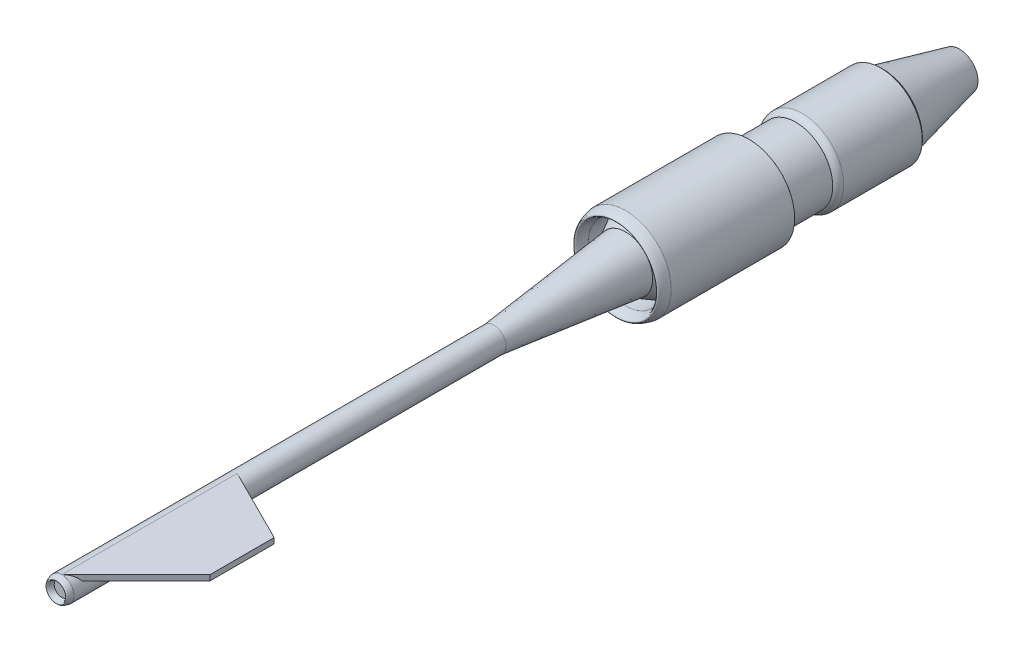
SolidWorks part; units mm, degrees
ref_plane "Front Plane" through (0, 0, 0) normal (0, 0, 1) x (1, 0, 0)
ref_plane "Top Plane" through (0, 0, 0) normal (0, 1, 0) x (1, 0, 0)
ref_plane "Right Plane" through (0, 0, 0) normal (1, 0, 0) x (0, 0, -1)
sketch "Sketch1" plane through (0, 0, 0) normal (0, 0, 1) x (1, 0, 0)
  circle A0 centre (0, 0) radius 416.25
  circle A1 centre (0, 0) radius 337.5
extrude "Boss-Extrude1" add sketch "Sketch1" against normal blind 1125
sketch "Sketch2" plane through (0, 0, 0) normal (1, 0, 0) x (0, 0, -1)
  line L0 (0, 416.25) -> (0, 337.5) construction
  line L1 (0, 337.5) -> (0, 376.875) construction
  line L2 (0, 376.875) -> (-90, 376.875) construction
  line L3 (0, 416.25) -> (0, 337.5)
  line L4 (0, 0) -> (98.8797, 0) construction
  spline S0 degree 2 poles (0, 337.5) (-180, 376.875) (0, 416.25) knots 0 0 0 1 1 1
revolve "Revolve1" add sketch "Sketch2" angle 360 about L4
ref_plane "Plane1" through (0, 0, 0) normal (0, 0, 1) x (1, 0, 0)
sketch "Sketch3" plane through (0, 0, 0) normal (0, 0, 1) x (1, 0, 0)
  circle A0 centre (0, 0) radius 247.5
sketch "Sketch4" plane through (0, 0, 0) normal (0, 1, 0) x (1, 0, 0)
  line L0 (0, 0) -> (0, -1200)
  line L1 (0, -1200) -> (112.5, -1200)
  line L2 (0, 0) -> (247.5, 0)
  line L3 (-247.5, 0) -> (247.5, 0) construction
  line L4 (-457.875, 0) -> (457.875, 0) construction
  line L5 (247.5, 0) -> (112.5, -1200)
revolve "Revolve2" add sketch "Sketch4" angle 360 about L0
sketch "Sketch5" plane through (0, 0, 1200) normal (0, 0, 1) x (1, 0, 0)
  circle A0 centre (0, 0) radius 112.5
extrude "Boss-Extrude2" add sketch "Sketch5" along normal blind 3937.5
sketch "Sketch14" plane through (0, 0, 0) normal (1, 0, 0) x (0, 0, -1)
  line L0 (-5137.5, 112.5) -> (-5137.5, 67.5)
  line L1 (-5137.5, 112.5) -> (-5137.5, -112.5) construction
  line L2 (-5137.5, 67.5) -> (-5137.5, 90)
  line L3 (-5137.5, 90) -> (-5187.5, 90) construction
  line L4 (-5137.5, 0) -> (-5198.2274, 0) construction
  line L5 (-5137.5, 112.5) -> (-5137.5, -112.5) construction
  spline S0 degree 2 poles (-5137.5, 67.5) (-5237.5, 90) (-5137.5, 112.5) knots 0 0 0 1 1 1
  dimension "D1" = 50
  dimension "D2" = 67.5
  dimension "D3" = 90
revolve "Revolve4" add sketch "Sketch14" angle 360 about L4 region at (0, 90, 5157.5)
sketch "Sketch15" plane through (0, 0, -1125) normal (0, 0, -1) x (-1, 0, 0)
  circle A0 centre (0, 0) radius 337.5
extrude "Boss-Extrude5" add sketch "Sketch15" along normal blind 486 separate body
sketch "Sketch16" plane through (0, 0, -1611) normal (0, 0, -1) x (-1, 0, 0)
  line L0 (0, 337.5) -> (0, 416.25) construction
  line L1 (0, 376.875) -> (79.8334, 376.875) construction
  circle A0 centre (0, 0) radius 337.5 construction
  circle A1 centre (0, 0) radius 337.5 construction
  circle A2 centre (0, 0) radius 416.25 construction
  circle A4 centre (0, 0) radius 376.875
extrude "Boss-Extrude6" add sketch "Sketch16" along normal blind 716
sketch "Sketch17" plane through (0, 0, 0) normal (1, 0, 0) x (0, 0, -1)
  line L0 (2327, 0) -> (3043, 0)
  line L1 (2327, -376.875) -> (2327, 376.875) construction
  line L2 (3043, 0) -> (3043, 168.75)
  line L3 (1611, 337.5) -> (2327, 337.5) construction
  line L4 (2327, 0) -> (2327, 337.5)
  line L5 (2327, 337.5) -> (3043, 168.75)
revolve "Revolve5" add sketch "Sketch17" angle 360 about L0
sketch "Sketch18" plane through (0, 0, 0) normal (1, 0, 0) x (0, 0, -1)
  line L0 (0, 247.5) -> (306.6324, 416.25)
  line L1 (1125, 416.25) -> (0, 416.25) construction
  line L2 (0, 247.5) -> (306.6324, 247.5)
  line L3 (306.6324, 247.5) -> (306.6324, 416.25)
  line L4 (0, 0) -> (306.6324, 0) construction
revolve "Revolve6" add sketch "Sketch18" angle 360 about L4
sketch "Sketch19" plane through (0, 0, 0) normal (1, 0, 0) x (0, 0, -1)
  line L1 (1611, 337.5) -> (1611, -337.5) construction
  line L2 (1611, 0) -> (1611, 337.5) construction
  line L3 (1611, 337.5) -> (1551, 337.5)
  line L4 (1611, 0) -> (1571, 0) construction
  line L5 (1611, 337.5) -> (1125, 337.5) construction
  line L6 (1611, 337.5) -> (1611, 376.875)
  line L7 (1611, 376.875) -> (1611, -376.875) construction
  arc A0 (1551, 337.5) -> (1611, 376.875) centre (1614.9642, 305.4325) cw
revolve "Revolve9" add sketch "Sketch19" angle 360 about L4
sketch "Sketch20" plane through (0, 0, 0) normal (1, 0, 0) x (0, 0, -1)
  line L0 (1125, 337.5) -> (1125, 416.25)
  line L1 (1125, 337.5) -> (1155, 337.5)
  line L2 (1551, 337.5) -> (1125, 337.5) construction
  line L3 (1125, 0) -> (1175, 0) construction
  line L4 (1125, -416.25) -> (1125, 416.25) construction
  conic Q0 (1155, 337.5) -> (1125, 416.25) control (1155, 382.5893) rho 0.44632
revolve "Revolve11" add sketch "Sketch20" angle 360 about L3
sketch "Sketch21" plane through (0, 0, 0) normal (1, 0, 0) x (0, 0, -1)
  line L0 (2327, 337.5) -> (2327, 376.875)
  line L1 (2327, 0) -> (2377, 0) construction
  line L2 (2327, -376.875) -> (2327, 376.875) construction
  line L3 (2327, 337.5) -> (2356.2, 330.618)
  line L4 (3043, 168.75) -> (2327, 337.5) construction
  conic Q0 (2327, 376.875) -> (2356.2, 330.618) control (2356.2, 357.1875) rho 0.453502
revolve "Revolve12" add sketch "Sketch21" angle 360 about L1
sketch3d "3DSketch1"
  line L0 (1.7689, 112.4861, 5137.5) -> (-673.2311, 112.4861, 5137.5) construction
  circle A0 centre (0, 0, 5137.5) radius 112.5 construction
  point P2 (0, 0, 5250)
ref_plane "Plane2" through (0, 112.4861, 0) normal (0, 1, 0) x (1, 0, 0)
sketch "Sketch22" plane through (0, 112.4861, 0) normal (0, 1, 0) x (1, 0, 0)
  line L0 (1.7689, -5137.5) -> (1.7689, -3540)
  line L1 (-673.2311, -5137.5) -> (-673.2311, -4462.5) construction
  line L2 (-673.2311, -4462.5) -> (1.7689, -4462.5) construction
  line L3 (-673.2311, -4462.5) -> (1.7689, -5137.5)
  line L4 (-673.2311, -4462.5) -> (-673.2311, -3877.5)
  line L5 (-673.2311, -3877.5) -> (1.7689, -3540)
  line L6 (676.7689, -3877.5) -> (1.7689, -3540)
  line L7 (676.7689, -4462.5) -> (1.7689, -5137.5)
  line L8 (676.7689, -4462.5) -> (676.7689, -3877.5)
extrude "Boss-Extrude7" add sketch "Sketch22" against normal blind 50 contours L7 L8 L6 L0 region at (287.0782, 112.4861, 4267.4227)
sketch3d "3DSketch2"
  line L0 (0, 0, 0) -> (-416.25, 0, 0)
  line L1 (-416.25, 0, 0) -> (-416.25, 0, -1125)
  line L2 (0, 0, 0) -> (-409.9262, -72.2811, 0)
  line L3 (-409.9262, -72.2811, 0) -> (-416.438, -35.3508, 0)
  line L4 (-409.9262, -72.2811, 0) -> (-403.4144, -109.2113, 0)
  line L5 (0, 0, 0) -> (416.25, 0, 0)
  line L6 (416.25, 0, 0) -> (416.25, -37.5, 0)
  line L7 (416.25, 0, 0) -> (416.25, 37.5, 0)
  circle A1 centre (0, 0, 0) radius 416.25 construction
  circle A3 centre (0, 0, -1125) radius 416.25 construction
  arc A4 (-416.25, 0, 0) -> (-409.9262, -72.2811, 0) centre (0, 0, 0) ccw
  point P5 (0, 0, 416.25)
  point P10 (0, 0, -708.75)
  point P12 (0, 0, 416.25)
  dimension "D1" = 90
  dimension "D2" = 90
  dimension "D3" = 90
